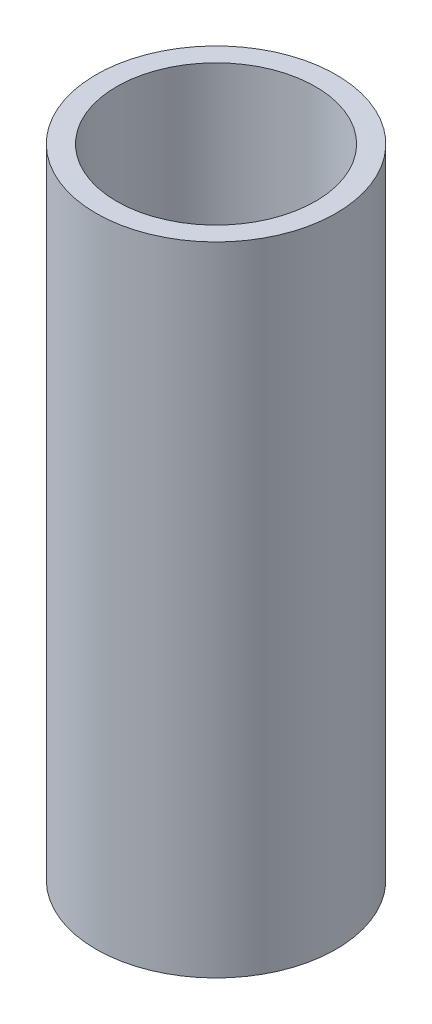
SolidWorks part; units mm, degrees
ref_plane "Front Plane" through (0, 0, 0) normal (0, 0, 1) x (1, 0, 0)
ref_plane "Top Plane" through (0, 0, 0) normal (0, 1, 0) x (1, 0, 0)
ref_plane "Right Plane" through (0, 0, 0) normal (1, 0, 0) x (0, 0, -1)
sketch "Sketch1" plane through (0, 0, 0) normal (0, 1, 0) x (1, 0, 0)
  circle A0 centre (0, 0) radius 52.5
  dimension "SLEEVE_OD" = 105
extrude "Boss-Extrude1" add sketch "Sketch1" along normal blind 278.7362
sketch "Sketch2" plane through (0, 0, 0) normal (0, 1, 0) x (1, 0, 0)
  circle A0 centre (0, 0) radius 43.472
  dimension "BORE_D" = 86.944
extrude "Cut-Extrude1" cut sketch "Sketch2" along normal through all
chamfer "Chamfer1" distance 3.6537 angle 60 rebuild error yes
